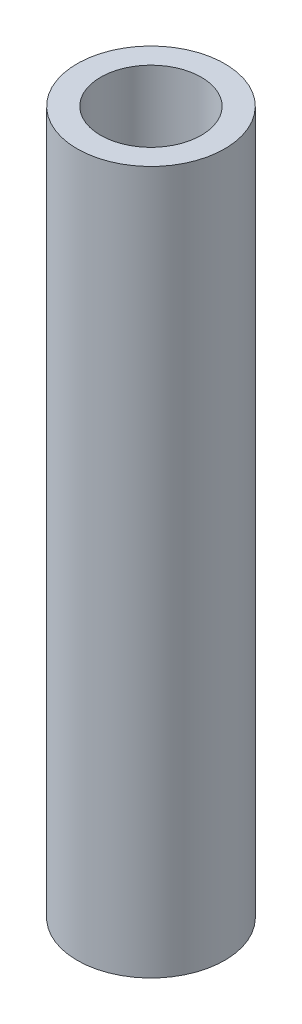
SolidWorks part; units mm, degrees
material "Silicon"
ref_plane "Front Plane" through (0, 0, 0) normal (0, 0, 1) x (1, 0, 0)
ref_plane "Top Plane" through (0, 0, 0) normal (0, 1, 0) x (1, 0, 0)
ref_plane "Right Plane" through (0, 0, 0) normal (1, 0, 0) x (0, 0, -1)
sketch "Sketch1" plane through (0, 0, 0) normal (0, 1, 0) x (1, 0, 0)
  circle A0 centre (0, 0) radius 27.3
  circle A1 centre (0, 0) radius 40
  dimension "D1" = 80
  dimension "D2" = 12.7
extrude "Boss-Extrude1" add sketch "Sketch1" along normal blind 381
